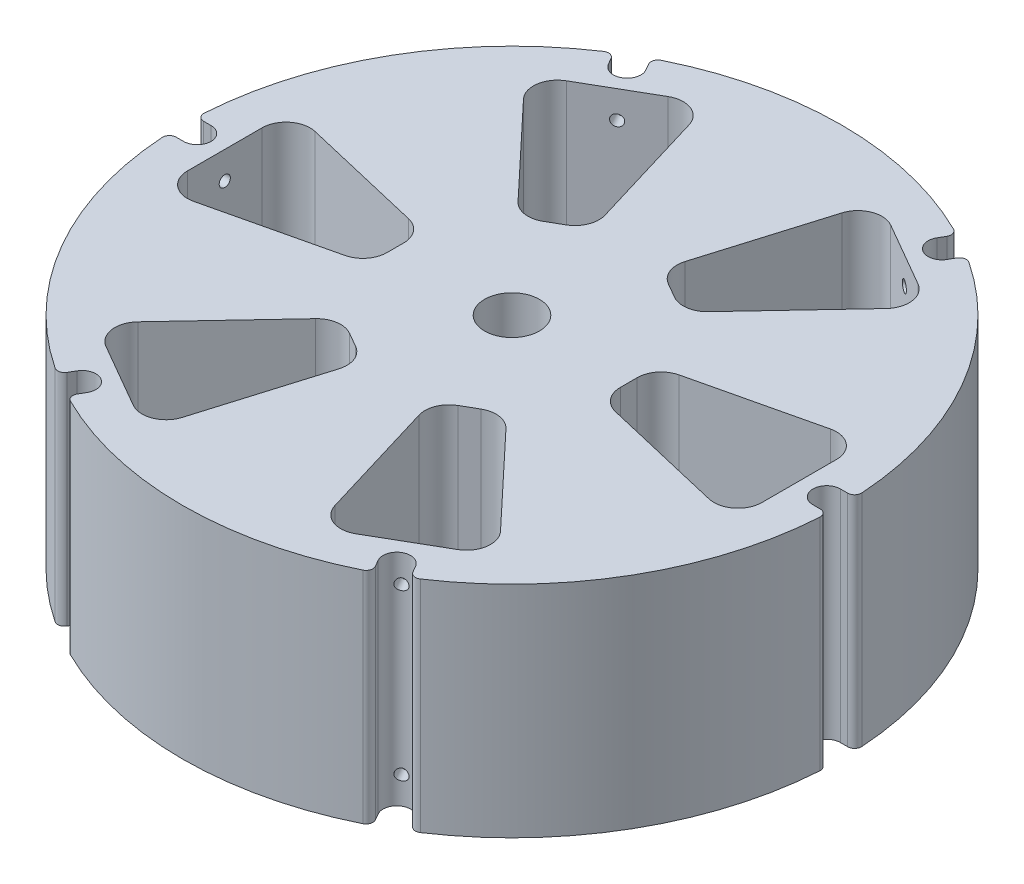
SolidWorks part; units mm, degrees
material "6061-T6 (SS)"
ref_plane "Front Plane" through (0, 0, 0) normal (0, 0, 1) x (1, 0, 0)
ref_plane "Top Plane" through (0, 0, 0) normal (0, 1, 0) x (1, 0, 0)
ref_plane "Right Plane" through (0, 0, 0) normal (1, 0, 0) x (0, 0, -1)
sketch "Sketch1" plane through (0, 0, 0) normal (0, 1, 0) x (1, 0, 0)
  circle A0 centre (0, 0) radius 76.2
  circle A1 centre (0, 0) radius 14.2875
  dimension "D1" = 152.4
  dimension "D2" = 28.575
extrude "Boss-Extrude1" add sketch "Sketch1" against normal mid plane 50.8
sketch "Sketch3" plane through (0, -25.4, 0) normal (0, -1, 0) x (-1, 0, 0)
  line L0 (-76.1338, 3.175) -> (-72.771, 3.175)
  line L1 (-76.1338, -3.175) -> (-72.771, -3.175)
  circle A0 centre (0, 0) radius 76.2 construction
  arc A1 (-72.771, 3.175) -> (-72.771, -3.175) centre (-72.771, 0) cw
  arc A2 (-76.1338, -3.175) -> (-76.1338, 3.175) centre (0, 0) cw
  point P9 (-69.596, 0)
  point P13 (-76.2, 0)
  dimension "D1" = 6.35
  dimension "D2" = 6.604
extrude "Cut-Extrude1" cut sketch "Sketch3" against normal through all
sketch "Sketch4" plane through (0, -25.4, 0) normal (0, -1, 0) x (-1, 0, 0)
  line L0 (-66.421, 15.6285) -> (-66.421, -15.6285)
  line L1 (-66.421, -15.6285) -> (-26.9875, -6.35)
  line L2 (-26.9875, -6.35) -> (-26.9875, 6.35)
  line L3 (-26.9875, 6.35) -> (-66.421, 15.6285)
  line L4 (-66.421, 0) -> (0, 0) construction
  line L5 (-26.9875, -6.35) -> (0, 0) construction
  circle A2 centre (0, 0) radius 14.2875 construction
  point P12 (-14.2875, 0)
  point P14 (-26.9875, 0)
  dimension "D1" = 3.175
  dimension "D2" = 12.7
  dimension "D4" = 12.7
extrude "Cut-Extrude2" cut sketch "Sketch4" against normal through all
hole_wizard "#5-40 Tapped Hole1" positions "Sketch5" profile "Sketch6" tap size "#5-40" standard "ANSI Inch" end condition through all
sketch "Sketch5" plane through (66.421, 0, 0) normal (-1, 0, 0) x (0, 0, 1)
  line L0 (-15.6285, -25.4) -> (15.6285, -25.4) construction
  point P0 (0, -19.05)
  dimension "D1" = 6.35
sketch "Sketch6" plane through (66.421, -19.05, 0) normal (0, 1, 0) x (0, 0, 1)
  line L0 (0, 0) -> (0, 9.7128)
  line L1 (0, 9.7128) -> (1.289, 9.7128)
  line L2 (1.289, 9.7128) -> (1.289, 0)
  line L5 (1.289, 0) -> (0, 0)
  line L11 (0, -6.35) -> (0, 107.95) construction
  dimension "Thru Tap Drill Dia." = 2.5781
  dimension "Thru Tap Drill Depth" = 9.7128
cosmetic thread "Hole Thread1" parameters "D2"=3.175
fillet "Fillet1" radius 1.5875 2 edges at (76.1338, 0, 3.175) (76.1338, 0, -3.175)
fillet "Fillet2" radius 5.5562 4 edges at (66.421, 0, 15.6285) (66.421, 0, -15.6285) (26.9875, 0, 6.35) (26.9875, 0, -6.35)
mirror "Mirror1" about plane through (0, 0, 0) normal (0, 1, 0) of "#5-40 Tapped Hole1"
cosmetic thread "Hole Thread7" parameters "D2"=3.175
pattern_circular "CirPattern1" count 6 over 360 about axis through (0, -25.4, 0) along (0, 1, 0) of "Cut-Extrude1", "Cut-Extrude2", "Fillet2", "Fillet1", "#5-40 Tapped Hole1", "Mirror1"
cosmetic thread "Hole Thread2" parameters "D2"=3.175
cosmetic thread "Hole Thread3" parameters "D2"=3.175
cosmetic thread "Hole Thread4" parameters "D2"=3.175
cosmetic thread "Hole Thread5" parameters "D2"=3.175
cosmetic thread "Hole Thread6" parameters "D2"=3.175
cosmetic thread "Hole Thread8" parameters "D2"=3.175
cosmetic thread "Hole Thread9" parameters "D2"=3.175
cosmetic thread "Hole Thread10" parameters "D2"=3.175
cosmetic thread "Hole Thread11" parameters "D2"=3.175
cosmetic thread "Hole Thread12" parameters "D2"=3.175
sketch "Sketch7" plane through (0, 25.4, 0) normal (0, 1, 0) x (1, 0, 0)
  circle A0 centre (0, 0) radius 6.35
  circle A1 centre (0, 0) radius 14.2875
  circle A2 centre (0, 0) radius 14.2875 construction
  dimension "D1" = 12.7
extrude "Boss-Extrude2" add sketch "Sketch7" against normal offset from surface (10.668 mm away) 40.132 up to face at (23.0798, -25.4, 39.9754)
sketch "Sketch8" plane through (0, -25.4, 0) normal (0, -1, 0) x (1, 0, 0)
  circle A0 centre (0, 0) radius 25.4
  point P3 (0, 0)
  dimension "D1" = 50.8
extrude "Cut-Extrude3" cut sketch "Sketch8" against normal blind 25.4
